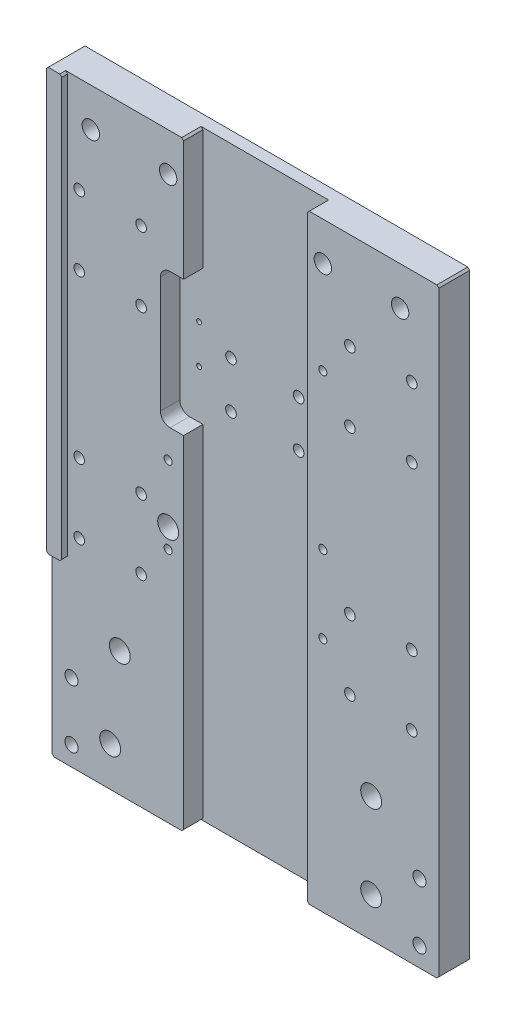
SolidWorks part; units mm, degrees
material "6061-T6 (SS)"
ref_plane "Front Plane" through (0, 0, 0) normal (0, 0, 1) x (1, 0, 0)
ref_plane "Top Plane" through (0, 0, 0) normal (0, 1, 0) x (1, 0, 0)
ref_plane "Right Plane" through (0, 0, 0) normal (1, 0, 0) x (0, 0, -1)
sketch "Sketch1" plane through (0, 0, 0) normal (0, 0, 1) x (1, 0, 0)
  line L0 (0, -10.4775) -> (0, 10.4775) construction
  line L1 (-70, 60) -> (70, 60) construction
  line L2 (-70, 60) -> (-70, -60) construction
  line L3 (-70, -60) -> (70, -60) construction
  line L4 (70, 60) -> (70, -60) construction
  line L5 (-70, 60) -> (70, -60) construction
  line L6 (-70, -60) -> (70, 60) construction
  line L7 (-86, 78) -> (-54, 78) construction
  line L8 (-86, 78) -> (-86, 42) construction
  line L9 (-86, 42) -> (-54, 42) construction
  line L10 (-54, 78) -> (-54, 42) construction
  line L11 (-86, 78) -> (-54, 42) construction
  line L12 (-86, 42) -> (-54, 78) construction
  line L13 (-100, 128) -> (100, 128)
  line L14 (-100, 128) -> (-100, -182.5)
  line L15 (-100, -182.5) -> (100, -182.5)
  line L16 (100, 128) -> (100, -182.5)
  line L17 (-100, -97.5) -> (100, -97.5) construction
  line L18 (-100, 88) -> (100, 88) construction
  line L19 (54, -42) -> (86, -42) construction
  line L20 (54, -42) -> (54, -78) construction
  line L21 (54, -78) -> (86, -78) construction
  line L22 (86, -42) -> (86, -78) construction
  line L23 (54, -42) -> (86, -78) construction
  line L24 (54, -78) -> (86, -42) construction
  line L25 (35.5, -12.5) -> (54.5, -12.5) construction
  line L26 (-17.5, 32) -> (17.5, 32) construction
  line L27 (-17.5, 32) -> (-17.5, 8) construction
  line L28 (-17.5, 8) -> (17.5, 8) construction
  line L29 (17.5, 32) -> (17.5, 8) construction
  line L30 (-17.5, 32) -> (17.5, 8) construction
  line L31 (-17.5, 8) -> (17.5, 32) construction
  line L32 (-100, -97.5) -> (100, -182.5) construction
  point P0 (0, 0)
  point P14 (0, -182.5)
  point P23 (0, 20)
  point P33 (0, -140)
  point P35 (45, -12.5)
  dimension "D1" = 120
  dimension "D2" = 140
  dimension "D3" = 36
  dimension "D4" = 32
  dimension "D5" = 85
  dimension "D6" = 19.5
  dimension "D7" = 40
  dimension "D8" = 10
  dimension "D9" = 200
  dimension "D10" = 24
  dimension "D11" = 35
  dimension "D12" = 20
  dimension "D13" = 19
  dimension "D14" = 45
  dimension "D15" = 47.5
  dimension "D16" = 140
  dimension "D17" = 310.5
extrude "Boss-Extrude1" add sketch "Sketch1" along normal blind 19.05
sketch "Sketch2" plane through (0, 0, 19.05) normal (0, 0, 1) x (1, 0, 0)
  line L0 (100, 128) -> (-100, 128) construction
  line L1 (-92, 128) -> (100, 128)
  line L2 (-92, 128) -> (-92, -90)
  line L3 (-100, -182.5) -> (100, -182.5)
  line L4 (100, 128) -> (100, -182.5)
  line L5 (-92, -90) -> (-100, -90)
  line L6 (-100, 128) -> (-100, -182.5) construction
  line L7 (-70, 60) -> (-70, -60) construction
  line L8 (-100, -90) -> (-100, -182.5)
  line L9 (-70, -60) -> (70, -60) construction
  dimension "D1" = 22
  dimension "D2" = 30
extrude "Cut-Extrude1" cut sketch "Sketch2" against normal offset from surface (3.05 mm away) 16 up to face at (0, -27.25, 0)
sketch "Sketch3" plane through (0, 0, 16) normal (0, 0, 1) x (1, 0, 0)
  line L0 (-100, 128) -> (100, 128) construction
  line L1 (-32, 128) -> (32, 128)
  line L2 (-32, 128) -> (-32, 65)
  line L3 (-32, -182.5) -> (32, -182.5)
  line L4 (32, 128) -> (32, -182.5)
  line L5 (-100, -182.5) -> (100, -182.5) construction
  line L6 (0, -10.4775) -> (0, 10.4775) construction
  line L7 (-32, 65) -> (-39, 65)
  line L8 (-44, 60) -> (-44, 0)
  line L9 (-39, -5) -> (-32, -5)
  line L10 (-32, -5) -> (-32, -182.5)
  line L12 (-34, 40) -> (-34, 20) construction
  line L13 (-44, 30) -> (-34, 30) construction
  arc A0 (-44, 0) -> (-39, -5) centre (-39, 0) ccw
  arc A1 (-39, 65) -> (-44, 60) centre (-39, 60) ccw
  point P8 (0, -182.5)
  point P20 (-44, -5)
  point P23 (-44, 65)
  dimension "D4" = 5
  dimension "D1" = 64
  dimension "D2" = 34
  dimension "D3" = 70
  dimension "D5" = 20
  dimension "D6" = 10
  dimension "D7" = 30
extrude "Cut-Extrude2" cut sketch "Sketch3" against normal blind 10
hole_wizard "M5 Clearance Hole2" positions "Sketch4" profile "Sketch5" hole size "M5" standard "ANSI Metric" end condition up to next
sketch "Sketch4" plane through (0, 0, 16) normal (0, 0, 1) x (1, 0, 0)
  point P0 (54, -42)
  point P3 (86, -42)
  point P6 (86, -78)
  point P9 (54, -78)
sketch "Sketch5" plane through (54, -42, 16) normal (1, 0, 0) x (0, -1, 0)
  line L0 (0, 0) -> (0, 16)
  line L1 (0, 16) -> (2.75, 16)
  line L2 (2.75, 16) -> (2.75, 0)
  line L5 (2.75, 0) -> (0, 0)
  line L11 (0, -6.35) -> (0, 107.95) construction
  dimension "Thru Hole Dia." = 5.5
  dimension "Thru Hole Depth" = 16
mirror "Mirror1" about plane through (0, 0, 0) normal (0, 1, 0) of "M5 Clearance Hole2"
hole_wizard "M8 Clearance Hole1" positions "Sketch13" profile "Sketch14" hole size "M8" standard "ANSI Metric" end condition up to next
sketch "Sketch13" plane through (0, 0, 16) normal (0, 0, 1) x (1, 0, 0)
  line L0 (40, 108) -> (80, 108)
  line L2 (-100, 88) -> (100, 88) construction
  line L3 (0, -10.4775) -> (0, 10.4775) construction
  point P1 (40, 108)
  point P2 (80, 108)
  dimension "D1" = 20
  dimension "D2" = 40
  dimension "D3" = 40
sketch "Sketch14" plane through (40, 108, 16) normal (1, 0, 0) x (0, -1, 0)
  line L0 (0, 0) -> (0, 16)
  line L1 (0, 16) -> (4.5, 16)
  line L2 (4.5, 16) -> (4.5, 0)
  line L5 (4.5, 0) -> (0, 0)
  line L11 (0, -6.35) -> (0, 107.95) construction
  dimension "Thru Hole Dia." = 9
  dimension "Thru Hole Depth" = 16
hole_wizard "M5x0.8 Tapped Hole1" positions "Sketch15" profile "Sketch16" tap size "M5x0.8" standard "ANSI Metric" end condition up to next
sketch "Sketch15" plane through (0, 0, 16) normal (0, 0, 1) x (1, 0, 0)
  line L0 (40, 60) -> (40, -20)
  line L1 (40, -20) -> (40, -60)
  line L3 (-70, -60) -> (70, -60) construction
  line L4 (-70, 60) -> (70, 60) construction
  point P0 (40, 60)
  point P1 (40, -20)
  point P3 (40, -60)
  dimension "D1" = 40
  dimension "D2" = 80
  dimension "D3" = 40
sketch "Sketch16" plane through (40, 60, 16) normal (1, 0, 0) x (0, -1, 0)
  line L0 (0, 0) -> (0, 16)
  line L1 (0, 16) -> (2.1, 16)
  line L2 (2.1, 16) -> (2.1, 0)
  line L5 (2.1, 0) -> (0, 0)
  line L11 (0, -6.35) -> (0, 107.95) construction
  dimension "Thru Tap Drill Dia." = 4.2
  dimension "Thru Tap Drill Depth" = 16
cosmetic thread "Hole Thread5" parameters "D2"=5
cosmetic thread "Hole Thread6" parameters "D2"=5
cosmetic thread "Hole Thread7" parameters "D2"=5
mirror "Mirror2" about plane through (0, 0, 0) normal (1, 0, 0) of "M5x0.8 Tapped Hole1", "M8 Clearance Hole1", "Mirror1"
cosmetic thread "Hole Thread8" parameters "D2"=5
cosmetic thread "Hole Thread9" parameters "D2"=5
cosmetic thread "Hole Thread10" parameters "D2"=5
hole_wizard "M5 Clearance Hole1" positions "Sketch11" profile "Sketch12" hole size "M5" standard "ANSI Metric" end condition up to next
sketch "Sketch11" plane through (0, 0, 6) normal (0, 0, 1) x (1, 0, 0)
  point P0 (-17.5, 32)
  point P3 (17.5, 32)
  point P6 (17.5, 8)
  point P9 (-17.5, 8)
sketch "Sketch12" plane through (-17.5, 32, 6) normal (1, 0, 0) x (0, -1, 0)
  line L0 (0, 0) -> (0, 6)
  line L1 (0, 6) -> (2.75, 6)
  line L2 (2.75, 6) -> (2.75, 0)
  line L5 (2.75, 0) -> (0, 0)
  line L11 (0, -6.35) -> (0, 107.95) construction
  dimension "Thru Hole Dia." = 5.5
  dimension "Thru Hole Depth" = 6
hole_wizard "M12x1.25 Tapped Hole2" positions "Sketch17" profile "Sketch18" tap size "M12x1.25" standard "ANSI Metric" end condition up to next
sketch "Sketch17" plane through (0, 0, 16) normal (0, 0, 1) x (1, 0, 0)
  line L1 (-65, -118) -> (65, -118)
  line L2 (-65, -118) -> (-65, -162)
  line L3 (-65, -162) -> (65, -162)
  line L4 (65, -118) -> (65, -162)
  line L5 (-65, -118) -> (65, -162) construction
  line L6 (-65, -162) -> (65, -118) construction
  line L7 (-65, -162) -> (-70, -162)
  point P2 (65, -162)
  point P63 (-65, -118)
  point P65 (65, -118)
  point P72 (-70, -162)
  dimension "D1" = 44
  dimension "D2" = 130
  dimension "D3" = 5
sketch "Sketch18" plane through (65, -162, 16) normal (1, 0, 0) x (0, -1, 0)
  line L0 (0, 0) -> (0, 16)
  line L1 (0, 16) -> (5.4, 16)
  line L2 (5.4, 16) -> (5.4, 0)
  line L5 (5.4, 0) -> (0, 0)
  line L11 (0, -6.35) -> (0, 107.95) construction
  dimension "Thru Tap Drill Dia." = 10.8
  dimension "Thru Tap Drill Depth" = 16
cosmetic thread "Hole Thread11" parameters "D2"=12
cosmetic thread "Hole Thread12" parameters "D2"=12
cosmetic thread "Hole Thread13" parameters "D2"=12
cosmetic thread "Hole Thread14" parameters "D2"=12
hole_wizard "M8x1.25 Tapped Hole1" positions "Sketch20" profile "Sketch21" tap size "M8x1.25" standard "ANSI Metric" end condition up to next
sketch "Sketch20" plane through (0, 0, 0) normal (0, 0, -1) x (-1, 0, 0)
  line L1 (-90, -142.5) -> (90, -142.5)
  line L2 (-90, -142.5) -> (-90, -172.5)
  line L3 (-90, -172.5) -> (90, -172.5)
  line L4 (90, -142.5) -> (90, -172.5)
  line L5 (0, 10.4775) -> (0, -10.4775) construction
  line L6 (100, -182.5) -> (-100, -182.5) construction
  point P1 (-90, -142.5)
  point P2 (90, -172.5)
  point P205 (-90, -172.5)
  point P206 (90, -142.5)
  point P208 (0, -142.5)
  dimension "D1" = 180
  dimension "D2" = 10
  dimension "D3" = 30
sketch "Sketch21" plane through (90, -142.5, 0) normal (1, 0, 0) x (0, 1, 0)
  line L0 (0, 0) -> (0, 16)
  line L1 (0, 16) -> (3.4, 16)
  line L2 (3.4, 16) -> (3.4, 0)
  line L5 (3.4, 0) -> (0, 0)
  line L11 (0, -6.35) -> (0, 107.95) construction
  dimension "Thru Tap Drill Dia." = 6.8
  dimension "Thru Tap Drill Depth" = 16
cosmetic thread "Hole Thread15" parameters "D2"=8
cosmetic thread "Hole Thread16" parameters "D2"=8
cosmetic thread "Hole Thread17" parameters "D2"=8
cosmetic thread "Hole Thread18" parameters "D2"=8
hole_wizard "M3x0.5 Tapped Hole1" positions "Sketch22" profile "Sketch23" tap size "M3x0.5" standard "ANSI Metric" end condition up to next
sketch "Sketch22" plane through (0, 0, 6) normal (0, 0, 1) x (1, 0, 0)
  point P1 (-34, 40)
  point P2 (-34, 20)
sketch "Sketch23" plane through (-34, 40, 6) normal (1, 0, 0) x (0, -1, 0)
  line L0 (0, 0) -> (0, 6)
  line L1 (0, 6) -> (1.25, 6)
  line L2 (1.25, 6) -> (1.25, 0)
  line L5 (1.25, 0) -> (0, 0)
  line L11 (0, -6.35) -> (0, 107.95) construction
  dimension "Thru Tap Drill Dia." = 2.5
  dimension "Thru Tap Drill Depth" = 6
cosmetic thread "Hole Thread19" parameters "D2"=3
cosmetic thread "Hole Thread20" parameters "D2"=3
hole_wizard "M12x1.25 Tapped Hole1" positions "Sketch24" profile "Sketch25" tap size "M12x1.25" standard "ANSI Metric" end condition up to next
sketch "Sketch24" plane through (0, 0, 16) normal (0, 0, 1) x (1, 0, 0)
  line L0 (0, -10.4775) -> (0, 10.4775) construction
  point P0 (-40, -50)
  dimension "D1" = 40
  dimension "D2" = 50
sketch "Sketch25" plane through (-40, -50, 16) normal (1, 0, 0) x (0, -1, 0)
  line L0 (0, 0) -> (0, 16)
  line L1 (0, 16) -> (5.4, 16)
  line L2 (5.4, 16) -> (5.4, 0)
  line L5 (5.4, 0) -> (0, 0)
  line L11 (0, -6.35) -> (0, 107.95) construction
  dimension "Thru Tap Drill Dia." = 10.8
  dimension "Thru Tap Drill Depth" = 16
cosmetic thread "Hole Thread21" parameters "D2"=12
chamfer "Chamfer1" distance 1 11 edges at (100, 128, 8) (32, 128, 11) (-32, 128, 11) (-92, 128, 17.525) (-100, 128, 9.525) (32, -182.5, 11) (100, -182.5, 8) (-100, -182.5, 8) (-100, -90, 17.525) (-92, -90, 17.525) (-32, -182.5, 11)
